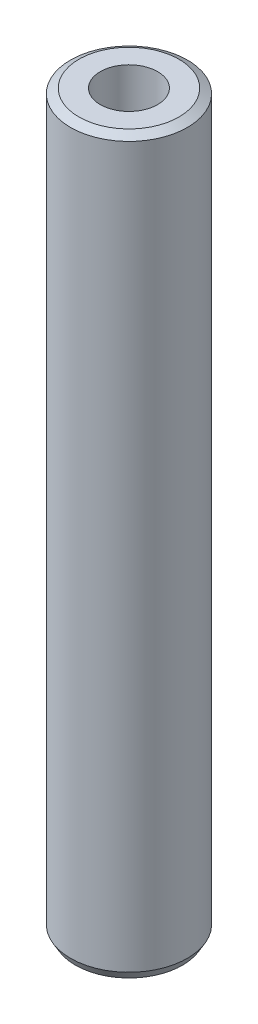
SolidWorks part; units mm, degrees
ref_plane "Front Plane" through (0, 0, 0) normal (0, 0, 1) x (1, 0, 0)
ref_plane "Top Plane" through (0, 0, 0) normal (0, 1, 0) x (1, 0, 0)
ref_plane "Right Plane" through (0, 0, 0) normal (1, 0, 0) x (0, 0, -1)
sketch "Sketch1" plane through (0, 0, 0) normal (0, 1, 0) x (1, 0, 0)
  circle A0 centre (0, 0) radius 27.5
  dimension "SHAFT_OD" = 55
extrude "Boss-Extrude1" add sketch "Sketch1" along normal blind 344.8061
sketch "Sketch2" plane through (0, 0, 0) normal (0, 1, 0) x (1, 0, 0)
  circle A0 centre (0, 0) radius 13.4741
  dimension "BORE_D" = 26.9482
extrude "Cut-Extrude1" cut sketch "Sketch2" along normal through all
chamfer "Chamfer1" distance 2.2837 angle 60 2 edges at (0, 344.8061, 27.5) (0, 0, 27.5) first distance on face at (0, 344.8061, 27.5) first distance on face at (0, 0, 13.4741)
